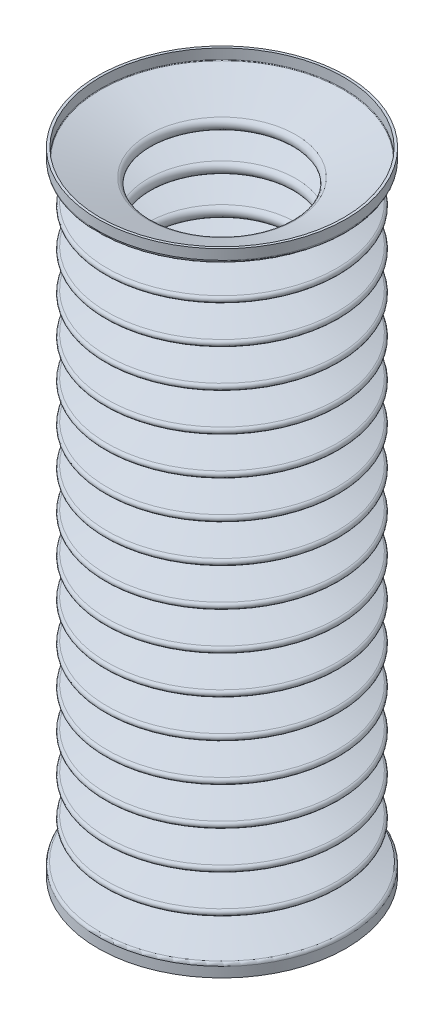
SolidWorks part; units mm, degrees
ref_plane "Front Plane" through (0, 0, 0) normal (0, 0, 1) x (1, 0, 0)
ref_plane "Top Plane" through (0, 0, 0) normal (0, 1, 0) x (1, 0, 0)
ref_plane "Right Plane" through (0, 0, 0) normal (1, 0, 0) x (0, 0, -1)
sketch "Sketch1" plane through (0, 0, 0) normal (0, 0, 1) x (1, 0, 0)
  line L0 (0, 0) -> (0, 304.8)
  line L1 (0, 0) -> (59.944, 0)
  line L2 (59.944, 0) -> (59.944, 4.8584)
  line L3 (31.496, 0) -> (31.496, 304.8) construction
  line L4 (58.8867, 6.3091) -> (36.0056, 13.6702)
  line L5 (36.0056, 16.5717) -> (55.4344, 22.8221)
  line L6 (31.496, 15.1209) -> (59.944, 15.1209) construction
  line L7 (59.944, 5.969) -> (59.944, 24.2729) construction
  line L8 (55.4344, 25.7236) -> (36.0056, 31.974)
  line L9 (36.0056, 34.8756) -> (55.4344, 41.126)
  line L10 (55.4344, 44.0275) -> (36.0056, 50.2779)
  line L11 (36.0056, 53.1795) -> (55.4344, 59.4299)
  line L12 (55.4344, 62.3314) -> (36.0056, 68.5818)
  line L13 (36.0056, 71.4833) -> (55.4344, 77.7337)
  line L14 (55.4344, 80.6353) -> (36.0056, 86.8857)
  line L15 (36.0056, 89.7872) -> (55.4344, 96.0376)
  line L16 (55.4344, 98.9391) -> (36.0056, 105.1895)
  line L17 (36.0056, 108.0911) -> (55.4344, 114.3415)
  line L18 (55.4344, 117.243) -> (36.0056, 123.4934)
  line L19 (36.0056, 126.395) -> (55.4344, 132.6454)
  line L20 (55.4344, 135.5469) -> (36.0056, 141.7973)
  line L21 (36.0056, 144.6988) -> (55.4344, 150.9492)
  line L22 (55.4344, 153.8508) -> (36.0056, 160.1012)
  line L23 (36.0056, 163.0027) -> (55.4344, 169.2531)
  line L24 (55.4344, 172.1546) -> (36.0056, 178.405)
  line L25 (36.0056, 181.3066) -> (55.4344, 187.557)
  line L26 (55.4344, 190.4585) -> (36.0056, 196.7089)
  line L27 (36.0056, 199.6105) -> (55.4344, 205.8609)
  line L28 (55.4344, 208.7624) -> (36.0056, 215.0128)
  line L29 (36.0056, 217.9143) -> (55.4344, 224.1647)
  line L30 (55.4344, 227.0663) -> (36.0056, 233.3167)
  line L31 (36.0056, 236.2182) -> (55.4344, 242.4686)
  line L32 (55.4344, 245.3701) -> (36.0056, 251.6205)
  line L33 (36.0056, 254.5221) -> (55.4344, 260.7725)
  line L34 (55.4344, 263.674) -> (36.0056, 269.9244)
  line L35 (36.0056, 272.826) -> (55.4344, 279.0764)
  line L36 (55.4344, 281.9779) -> (36.0056, 288.2283)
  line L37 (36.0056, 291.1298) -> (58.8867, 298.4909)
  line L38 (0, 152.4) -> (155.8281, 152.4) construction
  line L39 (59.944, 304.8) -> (59.944, 299.9416)
  line L40 (0, 304.8) -> (59.944, 304.8)
  arc A0 (59.944, 4.8584) -> (58.8867, 6.3091) centre (58.42, 4.8584) ccw
  arc A1 (59.944, 299.9416) -> (58.8867, 298.4909) centre (58.42, 299.9416) cw
  arc A2 (36.0056, 288.2283) -> (36.0056, 291.1298) centre (36.4723, 289.6791) cw
  arc A3 (55.4344, 279.0764) -> (55.4344, 281.9779) centre (54.9677, 280.5271) ccw
  arc A4 (36.0056, 269.9244) -> (36.0056, 272.826) centre (36.4723, 271.3752) cw
  arc A5 (55.4344, 260.7725) -> (55.4344, 263.674) centre (54.9677, 262.2232) ccw
  arc A6 (36.0056, 251.6205) -> (36.0056, 254.5221) centre (36.4723, 253.0713) cw
  arc A7 (55.4344, 242.4686) -> (55.4344, 245.3701) centre (54.9677, 243.9194) ccw
  arc A8 (36.0056, 233.3167) -> (36.0056, 236.2182) centre (36.4723, 234.7674) cw
  arc A9 (55.4344, 224.1647) -> (55.4344, 227.0663) centre (54.9677, 225.6155) ccw
  arc A10 (36.0056, 215.0128) -> (36.0056, 217.9143) centre (36.4723, 216.4636) cw
  arc A11 (55.4344, 205.8609) -> (55.4344, 208.7624) centre (54.9677, 207.3116) ccw
  arc A12 (36.0056, 196.7089) -> (36.0056, 199.6105) centre (36.4723, 198.1597) cw
  arc A13 (55.4344, 187.557) -> (55.4344, 190.4585) centre (54.9677, 189.0077) ccw
  arc A14 (36.0056, 178.405) -> (36.0056, 181.3066) centre (36.4723, 179.8558) cw
  arc A15 (55.4344, 169.2531) -> (55.4344, 172.1546) centre (54.9677, 170.7039) ccw
  arc A16 (36.0056, 160.1012) -> (36.0056, 163.0027) centre (36.4723, 161.5519) cw
  arc A17 (55.4344, 150.9492) -> (55.4344, 153.8508) centre (54.9677, 152.4) ccw
  arc A18 (36.0056, 141.7973) -> (36.0056, 144.6988) centre (36.4723, 143.2481) cw
  arc A19 (55.4344, 132.6454) -> (55.4344, 135.5469) centre (54.9677, 134.0961) ccw
  arc A20 (36.0056, 123.4934) -> (36.0056, 126.395) centre (36.4723, 124.9442) cw
  arc A21 (55.4344, 114.3415) -> (55.4344, 117.243) centre (54.9677, 115.7922) ccw
  arc A22 (36.0056, 105.1895) -> (36.0056, 108.0911) centre (36.4723, 106.6403) cw
  arc A23 (55.4344, 96.0376) -> (55.4344, 98.9391) centre (54.9677, 97.4884) ccw
  arc A24 (36.0056, 86.8857) -> (36.0056, 89.7872) centre (36.4723, 88.3364) cw
  arc A25 (55.4344, 77.7337) -> (55.4344, 80.6353) centre (54.9677, 79.1845) ccw
  arc A26 (36.0056, 68.5818) -> (36.0056, 71.4833) centre (36.4723, 70.0326) cw
  arc A27 (55.4344, 59.4299) -> (55.4344, 62.3314) centre (54.9677, 60.8806) ccw
  arc A28 (36.0056, 50.2779) -> (36.0056, 53.1795) centre (36.4723, 51.7287) cw
  arc A29 (55.4344, 41.126) -> (55.4344, 44.0275) centre (54.9677, 42.5767) ccw
  arc A30 (36.0056, 31.974) -> (36.0056, 34.8756) centre (36.4723, 33.4248) cw
  arc A31 (55.4344, 22.8221) -> (55.4344, 25.7236) centre (54.9677, 24.2729) ccw
  arc A32 (36.0056, 13.6702) -> (36.0056, 16.5717) centre (36.4723, 15.1209) cw
  point P12 (59.944, 15.1209)
  point P37 (59.944, 298.831)
  dimension "D7" = 1.524
  dimension "D1" = 59.944
  dimension "D2" = 5.969
  dimension "D3" = 304.8
  dimension "D4" = 31.496
  dimension "D6" = 18.3039
  dimension "D5" = 16
revolve "Revolve2" add sketch "Sketch1" angle 360 about L0
shell "Shell1" thickness 1.1938 removed face at (59.944, 0, 0) removed face at (59.944, 304.8, 0)
ref_axis "Axis1" through (0, 316.992, 0) along (0, -1, 0)
